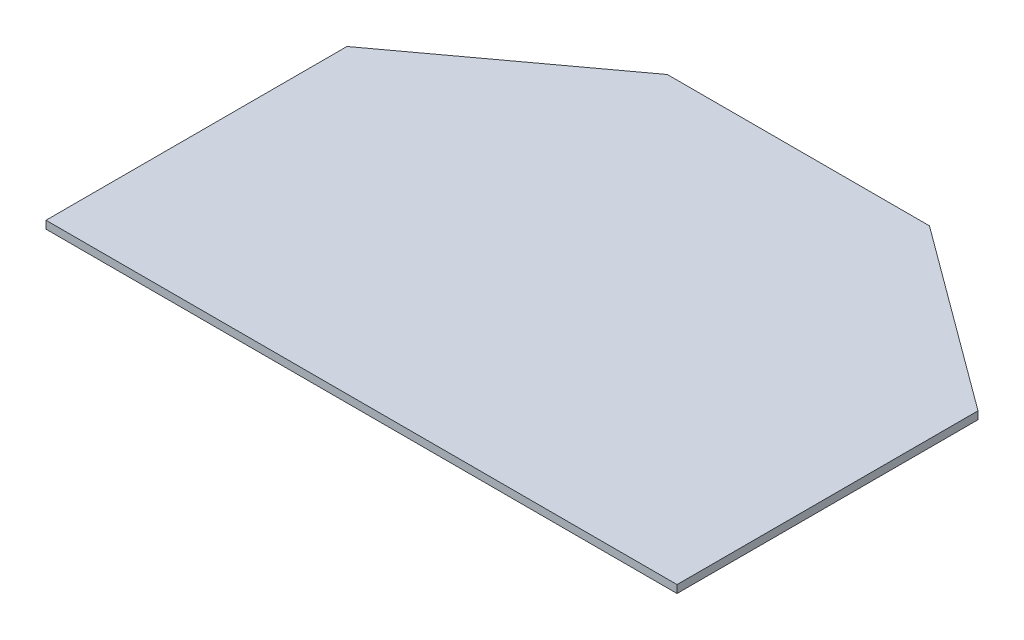
SolidWorks part; units mm, degrees
ref_plane "Front Plane" through (0, 0, 0) normal (0, 0, 1) x (1, 0, 0)
ref_plane "Top Plane" through (0, 0, 0) normal (0, 1, 0) x (1, 0, 0)
ref_plane "Right Plane" through (0, 0, 0) normal (1, 0, 0) x (0, 0, -1)
sketch "Sketch1" plane through (0, 0, 0) normal (0, 1, 0) x (1, 0, 0)
  line L0 (-65, 52) -> (-27, 80)
  line L2 (-65, 52) -> (-65, -10)
  line L3 (-27, 80) -> (0, 80)
  line L4 (0, -10) -> (0, 80)
  line L5 (0, -10) -> (-65, -10)
  line L6 (-59.397, 28.2843) -> (-43.8406, 43.8406) construction
  line L7 (-51.9976, -33.7676) -> (-63.9796, -15.3169) construction
  line L9 (0, 0) -> (-85, 0) construction
  line L10 (-43.8406, 43.8406) -> (0, 0) construction
  line L11 (-51.9976, -33.7676) -> (0, 0) construction
  circle A0 centre (0, 0) radius 85 construction
  circle A1 centre (-43.8406, 43.8406) radius 1.5 construction
  circle A4 centre (-63.9796, -15.3169) radius 1.5 construction
  dimension "D7" = 3
  dimension "D17" = 170
  dimension "D2" = 90
  dimension "D3" = 65
  dimension "D4" = 28
  dimension "D5" = 80
  dimension "D6" = 38
  dimension "D8" = 62
  dimension "D9" = 22
  dimension "D10" = 22
  dimension "D12" = 36.1594
  dimension "D14" = 45
  dimension "D15" = 33
extrude "Boss-Extrude1" add sketch "Sketch1" along normal blind 1.6
mirror "Mirror1" about plane through (0, 1.6, 10) normal (-1, 0, 0) of "Boss-Extrude1"
